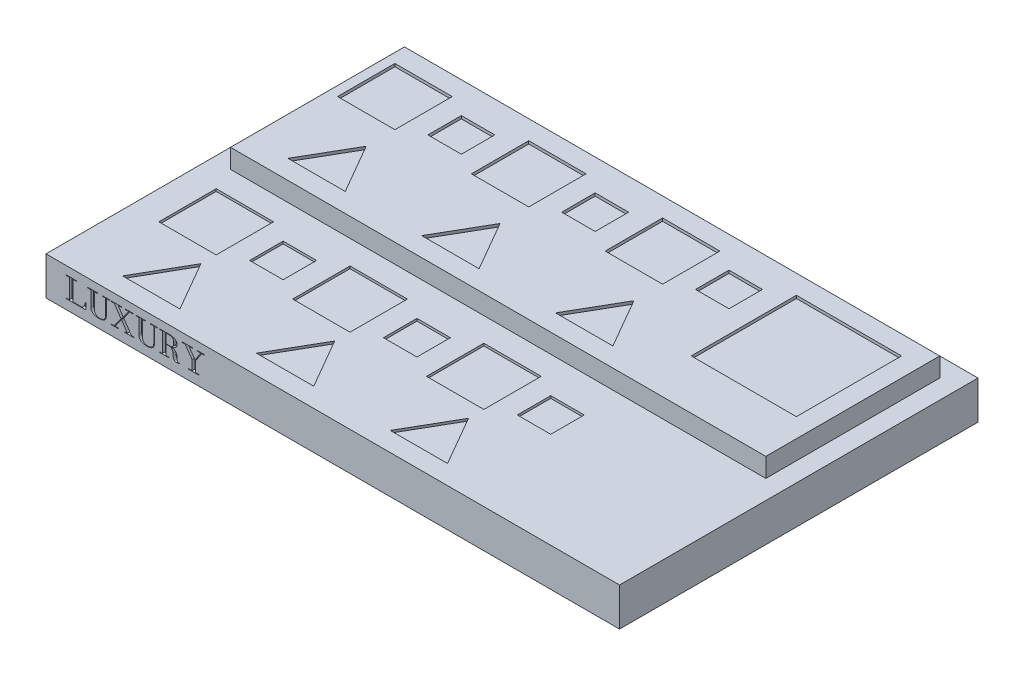
SolidWorks part; units mm, degrees
ref_plane "Front Plane" through (0, 0, 0) normal (0, 0, 1) x (1, 0, 0)
ref_plane "Top Plane" through (0, 0, 0) normal (0, 1, 0) x (1, 0, 0)
ref_plane "Right Plane" through (0, 0, 0) normal (1, 0, 0) x (0, 0, -1)
sketch "Sketch1" plane through (0, 0, 0) normal (0, 1, 0) x (1, 0, 0)
  line L21 (-300, 187.5) -> (300, 187.5)
  line L22 (-300, 187.5) -> (-300, -187.5)
  line L23 (-300, -187.5) -> (300, -187.5)
  line L24 (300, 187.5) -> (300, -187.5)
  line L25 (-300, 187.5) -> (300, -187.5) construction
  line L26 (-300, -187.5) -> (300, 187.5) construction
  point P0 (0, 0)
  dimension "D1" = 600
  dimension "D2" = 375
extrude "Boss-Extrude3" add sketch "Sketch1" against normal blind 40
sketch "Sketch2" plane through (0, 0, 187.5) normal (0, 0, 1) x (1, 0, 0)
  line L0 (-300, -40) -> (300, -40) construction
  line L1 (47.9838, -40) -> (47.9838, 0) construction
  line L2 (-280, -40) -> (-280, 0) construction
  line L3 (-300, 0) -> (300, 0) construction
  line L4 (-300, -40) -> (-300, 0) construction
  text T0 "LUXURY" font "BodoniFLF" height in points 70
  dimension "D1" = 10
  dimension "D2" = 20
extrude "Cut-Extrude1" cut sketch "Sketch2" against normal blind 3
sketch "Sketch3" plane through (0, 0, 0) normal (0, 1, 0) x (1, 0, 0)
  line L1 (-140, 167.5) -> (-280, 167.5)
  line L2 (-140, 167.5) -> (-140, -167.5)
  line L3 (-140, -167.5) -> (-280, -167.5)
  line L4 (-280, 167.5) -> (-280, -167.5)
  line L6 (300, 187.5) -> (-300, 187.5) construction
  line L7 (-300, 187.5) -> (-300, -187.5) construction
  line L15 (20, 167.5) -> (20, -167.5)
  line L16 (20, 167.5) -> (-120, 167.5)
  line L17 (-120, 167.5) -> (-120, -167.5)
  line L18 (20, -167.5) -> (-120, -167.5)
  line L19 (180, 167.5) -> (180, -167.5)
  line L20 (180, 167.5) -> (40, 167.5)
  line L21 (40, 167.5) -> (40, -167.5)
  line L22 (180, -167.5) -> (40, -167.5)
  line L23 (-300, -187.5) -> (300, -187.5) construction
  dimension "D1" = 140
  dimension "D2" = 3
  dimension "D3" = 20
  dimension "D4" = 20
  dimension "D6" = 20
  dimension "D5" = 20
sketch "Sketch5" plane through (0, 0, 0) normal (0, 1, 0) x (1, 0, 0)
  line L13 (-280, 167.5) -> (-280, -167.5) construction
  line L19 (-270, 147.5) -> (-210, 147.5)
  line L20 (-210, 57.5) -> (-240, 5.5385)
  line L21 (-240, 5.5385) -> (-180, 5.5385)
  line L22 (-180, 5.5385) -> (-210, 57.5)
  line L23 (-210, 147.5) -> (-210, 87.5)
  line L24 (-270, 87.5) -> (-210, 87.5)
  line L25 (-270, 147.5) -> (-270, 87.5)
  line L29 (-140, 167.5) -> (-140, -167.5) construction
  line L30 (-140, 167.5) -> (-280, 167.5) construction
  line L53 (300, -187.5) -> (300, 187.5) construction
  line L54 (300, 187.5) -> (-300, 187.5) construction
  circle A3 centre (-175, 130) radius 25
  point P37 (-160, 130)
  dimension "D22" = 35
  dimension "D14" = 30
  dimension "D17" = 60
  dimension "D19" = 10
  dimension "D20" = 20
extrude "Cut-Extrude2" cut sketch "Sketch5" against normal blind 3
sketch "Sketch6" plane through (0, 0, 0) normal (0, 1, 0) x (1, 0, 0)
  line L0 (-300, 187.5) -> (-300, -187.5) construction
  line L1 (-280, 167.5) -> (280, 167.5)
  line L2 (-280, 167.5) -> (-280, -14.4615)
  line L3 (-280, -14.4615) -> (280, -14.4615)
  line L4 (280, 167.5) -> (280, -14.4615)
  line L5 (300, -187.5) -> (300, 187.5) construction
  line L6 (300, 187.5) -> (-300, 187.5) construction
  line L7 (-240, 5.5385) -> (-180, 5.5385) construction
  dimension "D1" = 20
  dimension "D2" = 20
  dimension "D3" = 20
  dimension "D4" = 20
extrude "Boss-Extrude4" add sketch "Sketch6" along normal blind 20
sketch "Sketch8" plane through (0, 20, 0) normal (0, 1, 0) x (1, 0, 0)
  line L0 (-270, 87.5) -> (-270, 147.5)
  line L1 (-270, 147.5) -> (-210, 147.5)
  line L3 (-270, 87.5) -> (-210, 87.5)
  line L4 (-210, 147.5) -> (-210, 87.5)
  line L5 (-240, 5.5385) -> (-180, 5.5385)
  line L6 (-180, 5.5385) -> (-210, 57.5)
  line L7 (-210, 57.5) -> (-240, 5.5385)
  line L8 (-280, -14.4615) -> (280, -14.4615) construction
  line L9 (-280, 167.5) -> (-280, -14.4615) construction
  line L10 (280, 167.5) -> (-280, 167.5) construction
  line L11 (-130, 87.5) -> (-130, 147.5)
  line L12 (-130, 147.5) -> (-70, 147.5)
  line L13 (-70, 147.5) -> (-70, 87.5)
  line L14 (-130, 87.5) -> (-70, 87.5)
  line L15 (-100, 5.5385) -> (-40, 5.5385)
  line L16 (-40, 5.5385) -> (-70, 57.5)
  line L17 (-70, 57.5) -> (-100, 5.5385)
  line L18 (10, 87.5) -> (10, 147.5)
  line L19 (10, 147.5) -> (70, 147.5)
  line L20 (70, 147.5) -> (70, 87.5)
  line L21 (10, 87.5) -> (70, 87.5)
  line L22 (40, 5.5385) -> (100, 5.5385)
  line L23 (100, 5.5385) -> (70, 57.5)
  line L24 (70, 57.5) -> (40, 5.5385)
  line L26 (150, 147.5) -> (260, 147.5)
  line L27 (150, 147.5) -> (150, 37.5)
  line L28 (150, 37.5) -> (260, 37.5)
  line L29 (260, 147.5) -> (260, 37.5)
  line L30 (280, -14.4615) -> (280, 167.5) construction
  line L31 (-48, 135) -> (-48, 100)
  line L32 (-270, -39.4615) -> (-210, -39.4615)
  line L33 (-270, -39.4615) -> (-270, -99.4615)
  line L34 (-270, -99.4615) -> (-210, -99.4615)
  line L35 (-210, -39.4615) -> (-210, -99.4615)
  line L39 (-130, -39.4615) -> (-130, -99.4615)
  line L40 (-130, -39.4615) -> (-70, -39.4615)
  line L41 (-70, -39.4615) -> (-70, -99.4615)
  line L42 (-130, -99.4615) -> (-70, -99.4615)
  line L46 (10, -39.4615) -> (10, -99.4615)
  line L47 (10, -39.4615) -> (70, -39.4615)
  line L48 (70, -39.4615) -> (70, -99.4615)
  line L49 (10, -99.4615) -> (70, -99.4615)
  line L53 (-280, 167.5) -> (-280, -14.4615) construction
  line L54 (-188, 135) -> (-153, 135)
  line L55 (-188, 135) -> (-188, 100)
  line L56 (-188, 100) -> (-153, 100)
  line L57 (-153, 135) -> (-153, 100)
  line L58 (-48, 135) -> (-13, 135)
  line L59 (-13, 135) -> (-13, 100)
  line L60 (-48, 100) -> (-13, 100)
  line L61 (92, 135) -> (92, 100)
  line L62 (92, 135) -> (127, 135)
  line L63 (127, 135) -> (127, 100)
  line L64 (92, 100) -> (127, 100)
  line L65 (-300, 187.5) -> (-300, -187.5) construction
  line L66 (-240, -167.4487) -> (-180, -167.3974)
  line L67 (-180, -167.3974) -> (-210.0444, -115.4615)
  line L68 (-210.0444, -115.4615) -> (-240, -167.4487)
  line L69 (-100, -167.4487) -> (-40, -167.3974)
  line L70 (-40, -167.3974) -> (-70.0444, -115.4615)
  line L71 (-70.0444, -115.4615) -> (-100, -167.4487)
  line L72 (40, -167.4487) -> (100, -167.3974)
  line L73 (100, -167.3974) -> (69.9556, -115.4615)
  line L74 (69.9556, -115.4615) -> (40, -167.4487)
  line L75 (-47.5, -51.9615) -> (-47.5, -86.9615)
  line L76 (-187.5, -51.9615) -> (-152.5, -51.9615)
  line L77 (-187.5, -51.9615) -> (-187.5, -86.9615)
  line L78 (-187.5, -86.9615) -> (-152.5, -86.9615)
  line L79 (-152.5, -51.9615) -> (-152.5, -86.9615)
  line L80 (-47.5, -51.9615) -> (-12.5, -51.9615)
  line L81 (-12.5, -51.9615) -> (-12.5, -86.9615)
  line L82 (-47.5, -86.9615) -> (-12.5, -86.9615)
  line L83 (92.5, -51.9615) -> (92.5, -86.9615)
  line L84 (92.5, -51.9615) -> (127.5, -51.9615)
  line L85 (127.5, -51.9615) -> (127.5, -86.9615)
  line L86 (92.5, -86.9615) -> (127.5, -86.9615)
  circle A1 centre (-210, 22.859) radius 17.3205 construction
  circle A10 centre (-210.0148, -150.1025) radius 17.3205 construction
  point P20 (-210, 117.5)
  point P33 (-188, 117.5)
  point P47 (-70, 117.5)
  point P81 (-187.5, -69.4615)
  point P82 (-210, -69.4615)
  dimension "D2" = 35
  dimension "D3" = 20
  dimension "D6" = 22
  dimension "D19" = 20
  dimension "D1" = 60
  dimension "D4" = 10
  dimension "D5" = 20
  dimension "D8" = 80
  dimension "D9" = 110
  dimension "D10" = 20
  dimension "D11" = 20
  dimension "D12" = 3
  dimension "D13" = 22
  dimension "D14" = 3
  dimension "D15" = 10
  dimension "D16" = 25
  dimension "D17" = 80
  dimension "D18" = 60
  dimension "D20" = 60
  dimension "D21" = 16
  dimension "D23" = 80
  dimension "D24" = 35
  dimension "D25" = 22.5
  dimension "D27" = 22.5
  dimension "D7" = 3
  dimension "D22" = 3
  dimension "D26" = 3
extrude "Cut-Extrude12" cut sketch "Sketch8" against normal blind 3 contours L4 L1 L0 L3 | L57 L54 L55 L56 | L23 L24 L22 | L29 L26 L27 L28 | L61 L64 L63 L62 | L18 L21 L20 L19 | L31 L60 L59 L58 | L7 L5 L6 | L17 L15 L16 | L11 L12 L13 L14 region at (-240, 20, -117.5) region at (40, 20, -117.5) region at (70, 20, -22.859) region at (205, 20, -92.5) region at (-30.5, 20, -117.5) region at (-170.5, 20, -117.5) region at (109.5, 20, -117.5)
extrude "Cut-Extrude13" cut sketch "Sketch8<7>" against normal offset from surface (22.5 mm away) 37.5 contours L35 L32 L33 L34 | L79 L76 L77 L78 | L39 L42 L41 L40 | L75 L82 L81 L80 | L46 L49 L48 L47 | L83 L86 L85 L84 | L73 L74 L72 | L70 L71 L69 | L67 L68 L66 region at (-240, 20, 69.4615) region at (-100, 20, 69.4615) region at (40, 20, 69.4615) region at (-210.0148, 20, 150.1025) region at (-70.0148, 20, 150.1025) region at (69.9852, 20, 150.1025) region at (-30, 20, 69.4615) region at (-170, 20, 69.4615) region at (110, 20, 69.4615) up to face at (0, -40, 0)
sketch "Sketch8<7>" plane through (0, 20, 0) normal (0, 1, 0) x (1, 0, 0) same geometry as "Sketch8"
